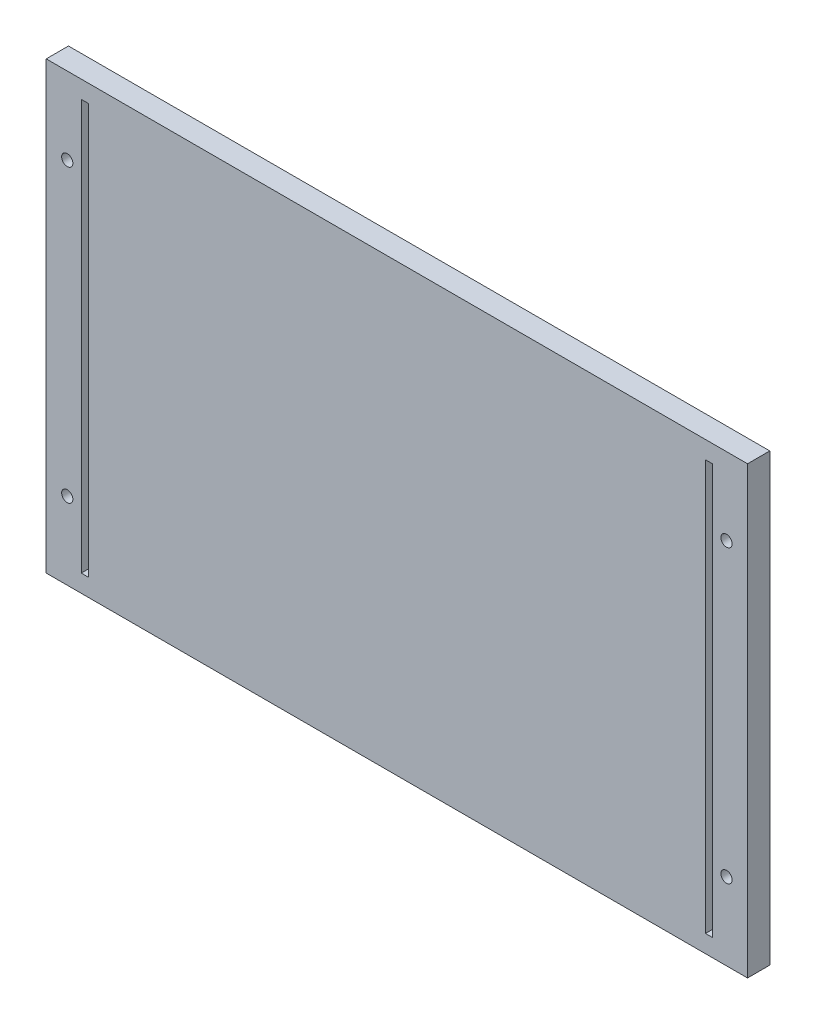
SolidWorks part; units mm, degrees
ref_plane "Front Plane" through (0, 0, 0) normal (0, 0, 1) x (1, 0, 0)
ref_plane "Top Plane" through (0, 0, 0) normal (0, 1, 0) x (1, 0, 0)
ref_plane "Right Plane" through (0, 0, 0) normal (1, 0, 0) x (0, 0, -1)
sketch "Sketch1" plane through (0, 0, 0) normal (0, 0, 1) x (1, 0, 0)
  line L0 (100, 127) -> (100, 0) construction
  line L1 (0, 0) -> (200, 0)
  line L2 (0, 0) -> (0, 127)
  line L3 (0, 127) -> (200, 127)
  line L4 (200, 0) -> (200, 127)
  line L5 (0, 63.5) -> (200, 63.5) construction
  circle A3 centre (6, 105) radius 1.6
  circle A7 centre (194, 105) radius 1.6
  circle A8 centre (194, 22) radius 1.6
  circle A9 centre (6, 22) radius 1.6
  dimension "D11" = 3.2
  dimension "D1" = 127
  dimension "D2" = 200
  dimension "D12" = 6
  dimension "D13" = 22
extrude "Wall" add sketch "Sketch1" along normal blind 6.35
sketch "Sketch2" [suppressed] plane through (0, 0, 6.35) normal (0, 0, 1) x (1, 0, 0)
  line L0 (135.35, 127) -> (135.35, 98.425) construction
  line L1 (270.7, 127) -> (0, 127) construction
  line L2 (135.35, 98.425) -> (66.6667, 98.425) construction
  line L3 (135.35, 98.425) -> (204.0333, 98.425) construction
  line L4 (0, 127) -> (0, 0) construction
  circle A0 centre (135.35, 98.425) radius 3.9687
  circle A1 centre (66.6667, 98.425) radius 3.9688
  circle A2 centre (204.0333, 98.425) radius 3.9687
  dimension "D2" = 7.9375
  dimension "D1" = 28.575
  dimension "D3" = 66.6667
extrude "RodSupportCutouts" [suppressed] cut sketch "Sketch2" against normal up to next
sketch "Sketch3" [suppressed] plane through (0, 0, 6.35) normal (0, 0, 1) x (1, 0, 0)
  line L1 (25.4, 88.9) -> (245.3, 88.9)
  line L2 (25.4, 88.9) -> (25.4, 114.3)
  line L3 (25.4, 114.3) -> (245.3, 114.3)
  line L4 (245.3, 88.9) -> (245.3, 114.3)
  line L5 (25.4, 88.9) -> (245.3, 114.3) construction
  line L6 (25.4, 114.3) -> (245.3, 88.9) construction
  line L7 (270.7, 127) -> (0, 127) construction
  line L8 (0, 127) -> (0, 0) construction
  point P0 (135.35, 101.6)
  point P9 (135.35, 127)
  dimension "D1" = 25.4
  dimension "D2" = 25.4
  dimension "D3" = 25.4
extrude "CannulaLargeCutout" [suppressed] cut sketch "Sketch3" against normal up to next
sketch "Sketch4" [suppressed] plane through (0, 0, 9.525) normal (0, 0, 1) x (1, 0, 0)
  line L0 (6, 103.5) -> (194, 103.5) construction
  line L1 (6, 105) -> (6, 22) construction
  line L2 (194, 105) -> (194, 22) construction
  line L3 (200, 127) -> (0, 127) construction
  line L4 (0, 127) -> (0, 0) construction
  circle A0 centre (60, 103.5) radius 6.35
  circle A1 centre (20, 103.5) radius 6.35
  circle A2 centre (100, 103.5) radius 6.35
  circle A3 centre (140, 103.5) radius 6.35
  circle A4 centre (60, 63.5) radius 6.35
  circle A5 centre (100, 63.5) radius 6.35
  circle A6 centre (140, 63.5) radius 6.35
  circle A7 centre (60, 23.5) radius 6.35
  circle A8 centre (100, 23.5) radius 6.35
  circle A9 centre (140, 23.5) radius 6.35
  circle A10 centre (20, 63.5) radius 6.35
  circle A11 centre (20, 23.5) radius 6.35
  circle A12 centre (180, 103.5) radius 6.35
  circle A13 centre (180, 63.5) radius 6.35
  circle A14 centre (180, 23.5) radius 6.35
  point P42 (100, 127)
  point P45 (0, 63.5)
  dimension "D3" = 12.7
  dimension "D1" = 5
  dimension "D2" = 3
extrude "CannulaHoles" [suppressed] cut sketch "Sketch4" against normal up to next
ref_plane "LeftBoundary" [suppressed] through (25.4, 0, 0) normal (-1, 0, 0) x (0, 0, 1)
ref_plane "RightBoundary" [suppressed] through (245.3, 0, 0) normal (1, 0, 0) x (0, 0, -1)
ref_plane "TopBoundary" [suppressed] through (0, 101.6, 0) normal (0, 1, 0) x (1, 0, 0)
ref_plane "BottomBoundary" [suppressed] through (0, 25.4, 0) normal (0, -1, 0) x (-1, 0, 0)
sketch "Sketch5" [suppressed] plane through (0, 0, 6.35) normal (0, 0, 1) x (1, 0, 0)
  line L4 (25.4, 3.4925) -> (25.4, -3.4925) construction
  line L5 (3.4925, 101.6) -> (-3.4925, 101.6) construction
  circle A0 centre (25.4, 101.6) radius 3.9687
  dimension "D1" = 7.9375
extrude "RodSupportCutout" [suppressed] cut sketch "Sketch5" along normal blind 3.35 from surface starting at face at (4.4, 22, 0)
pattern_linear "SupportPattern" [suppressed] count 7 spacing 36.65 count 5 spacing 19.05 of bodies 105
sketch "Sketch6" plane through (0, 0, 6.35) normal (0, 0, 1) x (1, 0, 0)
  line L0 (10, 122) -> (12, 122)
  line L1 (188, 122) -> (190, 122)
  line L2 (188, 122) -> (188, 5)
  line L3 (188, 5) -> (190, 5)
  line L4 (190, 122) -> (190, 5)
  line L5 (10, 122) -> (10, 5)
  line L6 (10, 5) -> (12, 5)
  line L7 (12, 122) -> (12, 5)
  line L8 (0, 127) -> (0, 0) construction
  line L9 (0, 0) -> (200, 0) construction
  line L10 (200, 0) -> (200, 127) construction
  line L11 (0, 0) -> (200, 0) construction
  point P7 (200, 57)
  dimension "D1" = 117
  dimension "D2" = 5
  dimension "D3" = 2
  dimension "D4" = 10
  dimension "D5" = 10
  dimension "D6" = 5
  dimension "D7" = 117
extrude "Cut-Extrude1" cut sketch "Sketch6" against normal through all
equation "\"Length\"= 283mm"
equation "\"Width\"= 225mm"
equation "\"WallThickness\"= 0.25in"
equation "\"UpperWaterJacketThickness\"= 28mm"
equation "\"SpacerHeight\"= 80.2mm"
equation "\"SpacerCornerWidth\"= 10mm"
equation "\"SpacerCornerHeight\"= 60.16mm"
equation "\"SpacerPegDiameter\"= 10mm"
equation "\"SpacerPegHeight\"= 10mm"
equation "\"TubingShort\"= 110mm"
equation "\"TubingLong\"= 175mm"
equation "\"PlateLength\"= 252mm"
equation "\"PlateWidth\"= 190mm"
equation "\"PlateHoleDiameter\"= 5.9mm"
equation "\"PlateHoleBottom\"= 2mm"
equation "\"PlateHoleSide\"= 1.55mm"
equation "\"PlateHoleSpacing\"= 3.1mm"
equation "\"PlateThickness\"= 1.55mm"
equation "\"ReservoirBottom\"= 12.5mm"
equation "\"ReservoirSupportWidth\"= 12mm"
equation "\"ReservoirSupportHeight\"= 15.1mm"
equation "\"ReservoirSupportPlacementHeight\"= 50mm"
equation "\"ReservoirHoleDiameter\"= 12.7mm"
equation "\"ReservoirHoleRight\"= 25mm"
equation "\"ReservoirHoleTop\"= \"ReservoirSupportPlacementHeight\""
equation "\"ReservoirHeight\"= 90mm"
equation "\"ReservoirPortBottom\"= 4mm"
equation "\"ReservoirPortTop\"= 10mm"
equation "\"ReservoirPortWidth\"= 101mm"
equation "\"CustomSpacerHeight\"= 5in"
equation "\"CustomSpacerRodHoleHeight\"= .75in"
equation "\"CustomSpacerRodHoleDiameter\"= .3125in"
equation "\"ScrewBlockSide\"= 12mm"
equation "\"ScrewBlockUpperHeight\"= 16mm"
equation "\"ScrewBlockLowerHeight\"= 16mm"
equation "\"InternalLength\"= 258mm"
equation "\"InternalWidth\"= 200mm"
equation "\"CustomSpacerPegHeight\"= 1in"
equation "\"CustomSpacerScrewBore\"=3.2mm"
equation "\"CustomSpacerScrewDepth\"=10mm"
equation "\"D1@Sketch1\"=\"CustomSpacerHeight\""
equation "\"D2@Sketch1\"=\"WallLength\""
equation "\"D11@Sketch1\"=\"CustomSpacerScrewBore\""
equation "\"D12@Sketch1\"   = \"ScrewBlockSide\"/2"
equation "\"D13@Sketch1\"=\"ScrewBlockUpperHeight\"+\"ScrewBlockSide\"/2"
equation "\"D1@Wall\" = \"WallThickness\""
equation "\"D1@Sketch2\"=\"CustomSpacerRodHoleHeight\" + \"CustomSpacerRodHoleDiameter\" +0.0625in"
equation "\"D2@Sketch2\"=\"CustomSpacerRodHoleDiameter\""
equation "\"D3@Sketch2\"=\"InternalWidth\" / 3"
equation "\"D1@Sketch3\"=1in"
equation "\"WallLength\"= \"InternalWidth\""
equation "\"D1@Sketch5\"=\"CustomSpacerRodHoleDiameter\""
equation "\"D1@RodSupportCutout\"      = \"WallThickness\" - 3"
